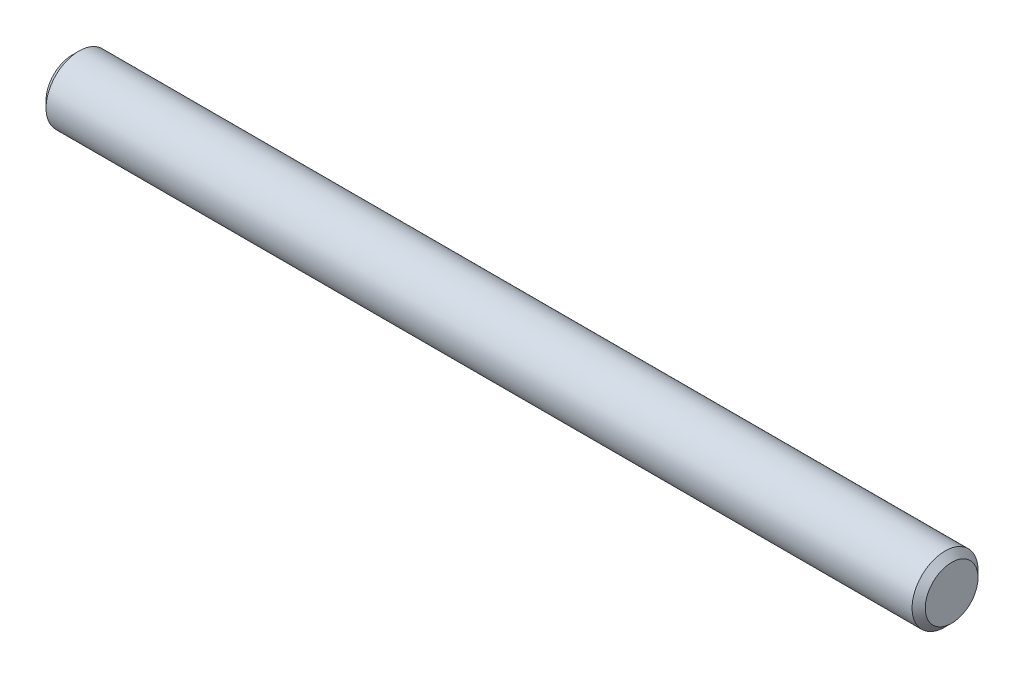
SolidWorks part; units mm, degrees
ref_plane "Front Plane" through (0, 0, 0) normal (0, 0, 1) x (1, 0, 0)
ref_plane "Top Plane" through (0, 0, 0) normal (0, 1, 0) x (1, 0, 0)
ref_plane "Right Plane" through (0, 0, 0) normal (1, 0, 0) x (0, 0, -1)
sketch "Sketch1" plane through (0, 0, 0) normal (1, 0, 0) x (0, 0, -1)
  circle A0 centre (0, 0) radius 0.75
  dimension "D1" = 1.5
extrude "Boss-Extrude1" add sketch "Sketch1" along normal blind 10 and the other way blind 10
chamfer "Chamfer1" distance 0.15 angle 45 2 edges at (-10, 0, -0.75) (10, 0, -0.75)
